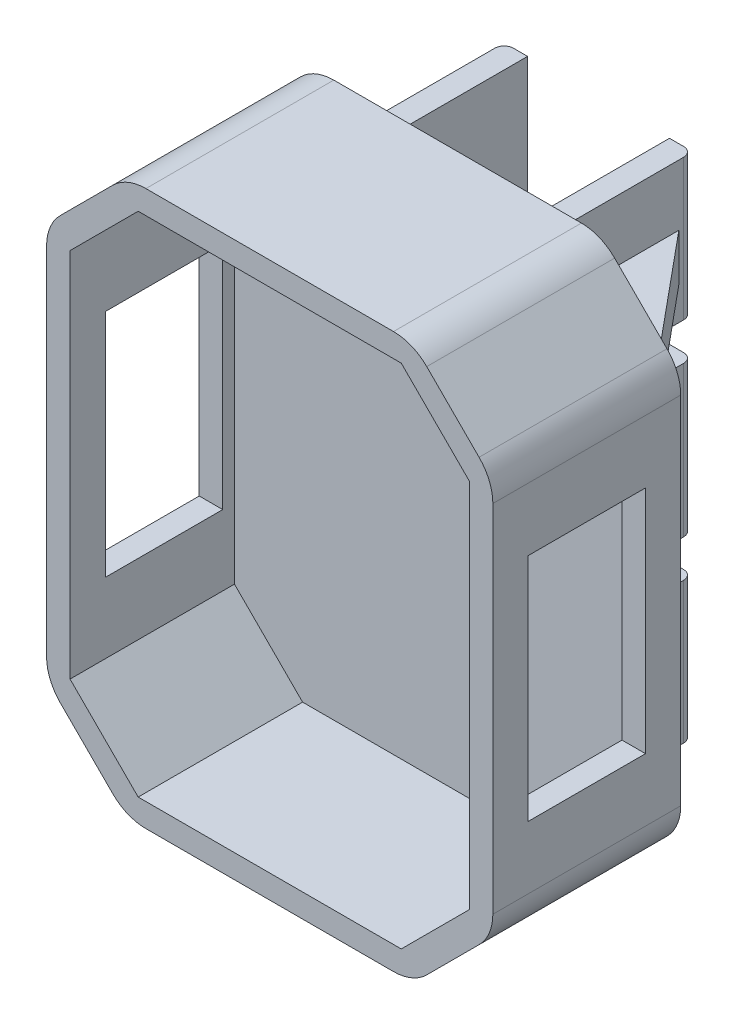
SolidWorks part; units mm, degrees
ref_plane "정면" through (0, 0, 0) normal (0, 0, 1) x (1, 0, 0)
ref_plane "윗면" through (0, 0, 0) normal (0, 1, 0) x (1, 0, 0)
ref_plane "우측면" through (0, 0, 0) normal (1, 0, 0) x (0, 0, -1)
sketch "스케치1" plane through (0, 0, 0) normal (0, 0, 1) x (1, 0, 0)
  line L0 (-184.6109, 0) -> (184.6109, 0) construction
  line L1 (0, 130.8629) -> (0, -130.8629) construction
  line L2 (-42.5, 39.5) -> (-42.5, -39.5)
  line L4 (42.5, -39.5) -> (42.5, 39.5)
  line L5 (28, 54) -> (-28, 54)
  line L6 (-28, -54) -> (28, -54) construction
  line L7 (-28, -54) -> (-28, -47.2663) construction
  line L8 (-28, -54) -> (28, -54)
  line L9 (-28, -54) -> (-42.5, -39.5)
  line L10 (28, -54) -> (42.5, -39.5)
  line L11 (28, 54) -> (42.5, 39.5)
  line L12 (-28, 54) -> (-42.5, 39.5)
  line L21 (-47.5, 42) -> (-47.5, -42)
  line L22 (-30.5, 59) -> (30.5, 59)
  line L23 (-30.5, 59) -> (-47.5, 42)
  line L24 (47.5, 42) -> (47.5, -42)
  line L25 (-30.5, -59) -> (30.5, -59)
  line L26 (30.5, 59) -> (47.5, 42)
  line L27 (47.5, -42) -> (30.5, -59)
  line L28 (-47.5, -42) -> (-30.5, -59)
  point P5 (0, 0)
  point P6 (0, 0)
  point P7 (-42.5, 0)
  point P8 (0, 54)
  point P15 (0, -54)
  point P16 (-47.5, 0)
  point P21 (0, 59)
  dimension "D1" = 79
  dimension "D2" = 20.5061
  dimension "D3" = 56
  dimension "D4" = 45
  dimension "D5" = 84
  dimension "D6" = 5
  dimension "D7" = 61
  dimension "D8" = 5
extrude "보스-돌출2" add sketch "스케치1" along normal blind 35
extrude "보스-돌출3" add sketch "스케치1<2>" against normal blind 5 contours L5 L12 L2 L9 L8 L10 L4 L11 | L21 L28 L25 L27 L24 L26 L22 L23 L12 L5 L11 L4 L10 L8 L9 L2 region at (0, 0, 0) region at (-37.9288, 49.4288, 0)
sketch "스케치1<2>" plane through (0, 0, 0) normal (0, 0, 1) x (1, 0, 0) same geometry as "스케치1"
sketch "스케치2" plane through (0, 0, 0) normal (1, 0, 0) x (0, 0, -1)
  line L0 (0, 0) -> (-35, 0) construction
  line L1 (-17.5, 0) -> (-17.5, -24.5) construction
  line L2 (-27.5, -24.5) -> (-7.5, -24.5)
  line L3 (-27.5, 24.5) -> (-7.5, 24.5)
  line L4 (-27.5, -24.5) -> (-27.5, 24.5)
  line L6 (-7.5, -24.5) -> (-2.5, -24.5)
  line L7 (-7.5, 24.5) -> (-2.5, 24.5)
  line L8 (-2.5, -24.5) -> (-2.5, 24.5)
  point P7 (-17.5, -24.5)
  dimension "D1" = 35
  dimension "D2" = 24.5
  dimension "D3" = 20
  dimension "D4" = 5
extrude "컷-돌출1" cut sketch "스케치2" against normal through all both and the other way through all
fillet "필렛1" radius 10 8 edges at (-47.5, -42, 15) (-47.5, 42, 15) (-30.5, 59, 15) (30.5, 59, 15) (47.5, 42, 15) (47.5, -42, 15) (30.5, -59, 15) (-30.5, -59, 15)
sketch "스케치3" plane through (0, 0, 0) normal (0, 0, 1) x (1, 0, 0)
  line L0 (0, 0) -> (15.1, 0) construction
  line L1 (15.1, 54) -> (15.1, -54)
  line L2 (28, 54) -> (-28, 54) construction
  line L3 (-28, -54) -> (28, -54) construction
  line L4 (20.1, 54) -> (20.1, -54)
  line L5 (0, 0) -> (0, 16.676) construction
  line L6 (-20.1, 54) -> (-20.1, -54)
  line L7 (-15.1, 54) -> (-15.1, -54)
  line L8 (-20.1, -54) -> (-15.1, -54)
  line L9 (15.1, -54) -> (20.1, -54)
  line L10 (15.1, 54) -> (20.1, 54)
  line L11 (-20.1, 54) -> (-15.1, 54)
  dimension "D1" = 15.1
  dimension "D2" = 5
extrude "보스-돌출4" add sketch "스케치3" against normal blind 35
sketch "스케치4" plane through (0, 0, 0) normal (1, 0, 0) x (0, 0, -1)
  line L0 (0, 0) -> (0, 20) construction
  line L1 (0, 20) -> (20, 20) construction
  line L2 (20, 16) -> (35, 16)
  line L3 (20, 24) -> (35, 24)
  line L4 (35, 16) -> (35, 24)
  line L5 (0, 0) -> (4.078, 0) construction
  line L6 (35, -16) -> (35, -24)
  line L7 (20, -24) -> (35, -24)
  line L8 (20, -16) -> (35, -16)
  arc A1 (20, 24) -> (20, 16) centre (20, 20) ccw
  arc A2 (20, -24) -> (20, -16) centre (20, -20) cw
  dimension "D3" = 4
  dimension "D1" = 20
  dimension "D2" = 20
  dimension "D4" = 15
extrude "컷-돌출2" cut sketch "스케치4" against normal through all both and the other way through all
sketch "스케치5" plane through (0, 0, 0) normal (0, 1, 0) x (1, 0, 0)
  line L0 (0, 0) -> (42.5, 0) construction
  line L1 (0, 0) -> (-42.5, 0) construction
  line L2 (20.1, 0) -> (20.1, 32) construction
  line L3 (42.5, 0) -> (42.5, 5) construction
  line L4 (42.5, 5) -> (20.1, 32)
  line L5 (0, 0) -> (0, -11.3842) construction
  dimension "D1" = 42.5
  dimension "D2" = 42.5
  dimension "D3" = 32
  dimension "D4" = 20.1
  dimension "D5" = 5
sketch "스케치7" plane through (0, 0, 0) normal (1, 0, 0) x (0, 0, -1)
  line L0 (0, 0) -> (0, 36.0378)
  line L1 (0, 36.0378) -> (26.8862, 36.0378)
ref_plane "평면1" through (0, 36.0378, 0) normal (0, 1, 0) x (1, 0, 0)
sketch "스케치8" plane through (0, 36.0378, 0) normal (0, 1, 0) x (1, 0, 0)
  line L0 (0, 0) -> (0, 5) construction
  line L1 (0, 0) -> (0, 26.8862) construction
  line L2 (0, 5) -> (42.5, 5) construction
  line L3 (20.1, 5) -> (20.1, 32) construction
  line L4 (42.5, 5) -> (20.1, 32)
  dimension "D1" = 5
  dimension "D2" = 42.5
  dimension "D3" = 27
  dimension "D4" = 20.1
rib "보강대5" sketch "스케치5" sketch "스케치5" thickness 10 extrusion direction parallel to sketch draft on no parameters "D1"=10
ref_plane "평면2" through (0, 0, 0) normal (1, 0, 0) x (0, 0, -1)
mirror "대칭 복사1" about plane through (0, 0, 0) normal (1, 0, 0) of "보강대5"
rib "보강대6" sketch "스케치8" sketch "스케치8" thickness 10 extrusion direction parallel to sketch draft on no parameters "D1"=10
mirror "대칭 복사2" about plane through (0, 0, 0) normal (1, 0, 0) of "보강대6"
mirror "대칭 복사3" about plane through (0, 0, 0) normal (0, 1, 0) of "대칭 복사2"
fillet "필렛2" radius 2 6 edges at (-20.1, 39, -35) (-20.1, 0, -35) (-20.1, -39, -35) (20.1, 39, -35) (20.1, 0, -35) (20.1, -39, -35)
